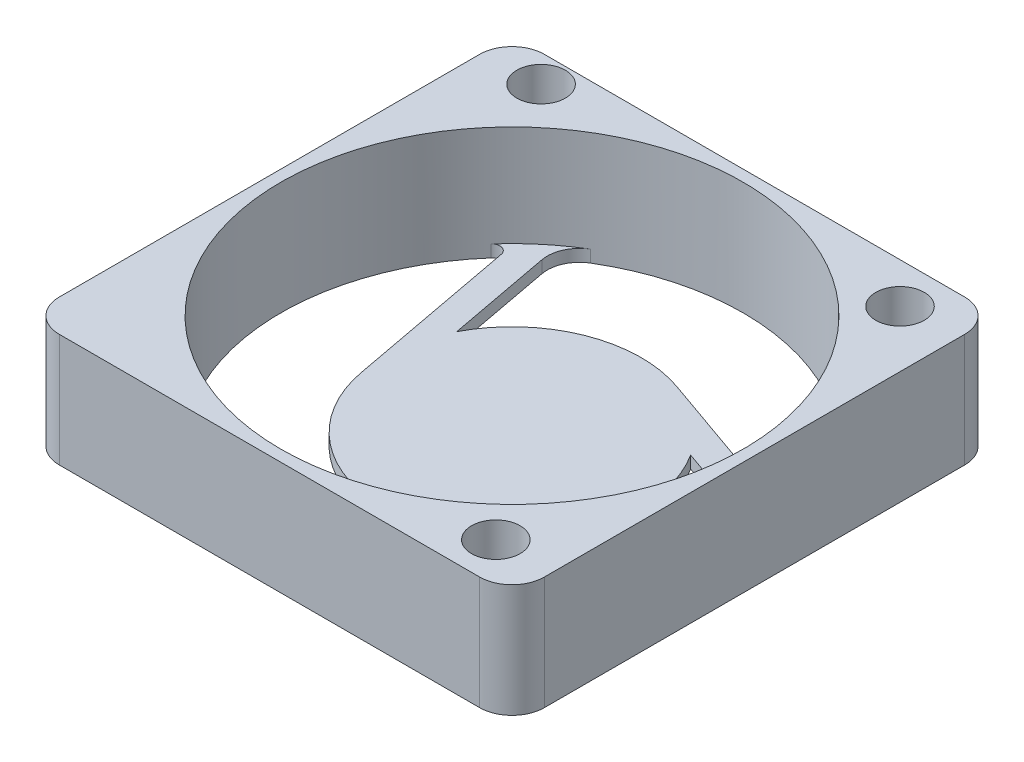
SolidWorks part; units mm, degrees
ref_plane "Front" through (0, 0, 0) normal (0, 0, 1) x (1, 0, 0)
ref_plane "Top" through (0, 0, 0) normal (0, 1, 0) x (1, 0, 0)
ref_plane "Right" through (0, 0, 0) normal (1, 0, 0) x (0, 0, -1)
sketch "Sketch1" plane through (0, 0, 0) normal (0, 1, 0) x (1, 0, 0)
  line L0 (-50, 0) -> (50, 0) construction
  line L1 (-13, -15) -> (13, -15)
  line L2 (-15, -13) -> (-15, 13)
  line L3 (-13, 15) -> (13, 15)
  line L4 (15, -13) -> (15, 13)
  line L5 (-15, 0) -> (0, 0) construction
  line L6 (0, 0) -> (0, 15) construction
  circle A0 centre (-11.5, 13.3) radius 1.5
  circle A1 centre (11.5, 12.5) radius 1.5
  circle A2 centre (11.5, -12.5) radius 1.5
  circle A3 centre (-11.5, -13.3) radius 1.5 construction
  arc A4 (13, -15) -> (15, -13) centre (13, -13) ccw
  arc A5 (-13, -15) -> (-15, -13) centre (-13, -13) cw
  arc A6 (13, 15) -> (15, 13) centre (13, 13) cw
  arc A7 (-15, 13) -> (-13, 15) centre (-13, 13) cw
  point P0 (0, 0)
  point P19 (15, -15)
  point P24 (15, 15)
  point P27 (-15, 15)
  dimension "D7" = 2
  dimension "D8" = 3
  dimension "D9" = 3
  dimension "D6" = 0.8
  dimension "D3" = 23
  dimension "D5" = 25
  dimension "D4" = 11.5
  dimension "D1" = 30
  dimension "D2" = 30
extrude "MainBlock" add sketch "Sketch1" along normal blind 7
sketch "Sketch2" plane through (0, 7, 0) normal (0, 1, 0) x (1, 0, 0)
  circle A0 centre (0, 0) radius 14.3
  dimension "D1" = 28.6
extrude "RotorSpace" cut sketch "Sketch2" against normal blind 6.25
sketch "Sketch3" plane through (0, 0.75, 0) normal (0, 1, 0) x (1, 0, 0)
  line L0 (2.6526, 7.5474) -> (13.8349, 3.6174)
  line L1 (14.2001, 1.6871) -> (6.7405, 4.3088)
  line L2 (5.21, -6.0709) -> (-3.7847, -13.7901)
  line L3 (-5.639, -13.1412) -> (0.3613, -7.9918)
  line L4 (-7.8626, -1.4765) -> (-10.0502, 10.1727)
  line L5 (-8.5611, 11.4541) -> (-7.1018, 3.683)
  circle A0 centre (0, 0) radius 8
  circle A1 centre (0, 0) radius 14.3 construction
  point P19 (0, 0)
  point P21 (0, 0)
  circle M4 centre (0, 0) radius 14.3
  dimension "D1" = 16
  dimension "D2" = 1.7
  dimension "D3" = 3
extrude "MotorBase" cut sketch "Sketch3" against normal up to surface (0.75 mm away) contours A0 M4 | A0 L0 M4 | A0 M4 region at (1.7147, 0.75, -9.6179) region at (7.472, 0.75, 6.294) region at (-9.1867, 0.75, 3.3239) up to face at (0, 0, 0)
fillet "Fillet1" radius 2 3 edges at (-8.5611, 0.375, -11.4541) (-5.639, 0.375, 13.1412) (14.2001, 0.375, -1.6871)
fillet "Fillet2" radius 0.5 3 edges at (-10.0502, 0.375, -10.1727) (13.8349, 0.375, -3.6174) (-3.7847, 0.375, 13.7901)
ref_plane "Plane1" through (0, 1.3, 0) normal (0, 1, 0) x (1, 0, 0)
